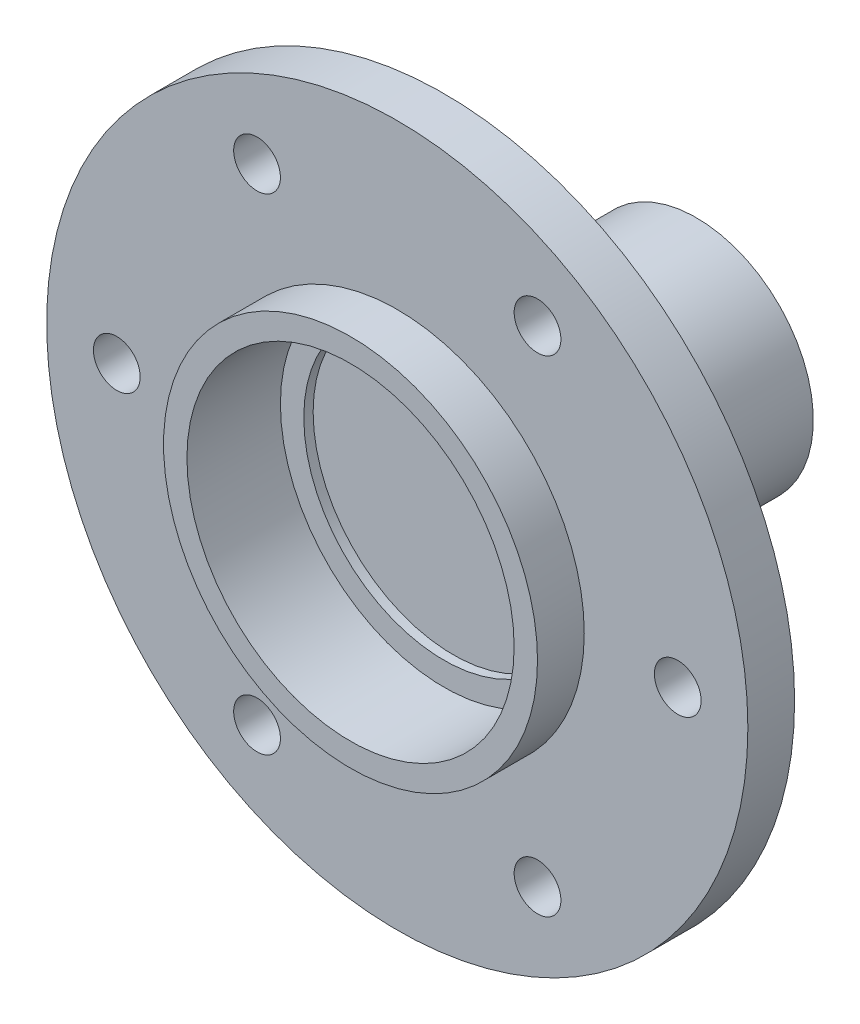
SolidWorks part; units mm, degrees
material "Gray Cast Iron"
ref_plane "Front Plane" through (0, 0, 0) normal (0, 0, 1) x (1, 0, 0)
ref_plane "Top Plane" through (0, 0, 0) normal (0, 1, 0) x (1, 0, 0)
ref_plane "Right Plane" through (0, 0, 0) normal (1, 0, 0) x (0, 0, -1)
sketch "Sketch1" plane through (0, 0, 0) normal (0, 0, 1) x (1, 0, 0)
  circle A0 centre (0, 0) radius 75
  dimension "D1" = 150
extrude "Boss-Extrude1" add sketch "Sketch1" along normal blind 10
sketch "Sketch2" plane through (0, 0, 0) normal (0, 0, -1) x (-1, 0, 0)
  circle A0 centre (0, 0) radius 45
  dimension "D1" = 90
extrude "Boss-Extrude2" add sketch "Sketch2" along normal blind 10
sketch "Sketch3" plane through (0, 0, -10) normal (0, 0, -1) x (-1, 0, 0)
  circle A0 centre (0, 0) radius 25
  dimension "D1" = 50
extrude "Boss-Extrude3" add sketch "Sketch3" along normal blind 44
fillet "Fillet1" radius 20 1 edges at (-25, 0, -10) type face fillet first side face at (-25, 0, -10) second side face at (-25, 0, -54)
sketch "Sketch4" plane through (0, 0, 10) normal (0, 0, 1) x (1, 0, 0)
  circle A0 centre (0, 0) radius 40
  dimension "D1" = 80
extrude "Boss-Extrude4" add sketch "Sketch4" along normal blind 10
sketch "Sketch5" plane through (0, 0, 20) normal (0, 0, 1) x (1, 0, 0)
  circle A0 centre (0, 0) radius 35
  dimension "D1" = 70
extrude "Cut-Extrude1" cut sketch "Sketch5" against normal blind 20
sketch "Sketch6" plane through (0, 0, 0) normal (0, 0, 1) x (1, 0, 0)
  circle A0 centre (0, 0) radius 30
  dimension "D1" = 60
extrude "Cut-Extrude2" cut sketch "Sketch6" against normal blind 2
sketch "Sketch7" plane through (0, 0, 10) normal (0, 0, 1) x (1, 0, 0)
  circle A0 centre (0, 0) radius 60 construction
  circle A1 centre (60, 0) radius 5
  circle A2 centre (30, -51.9615) radius 5
  circle A3 centre (-30, -51.9615) radius 5
  circle A4 centre (-60, 0) radius 5
  circle A5 centre (-30, 51.9615) radius 5
  circle A6 centre (30, 51.9615) radius 5
  point P17 (0, 0)
  dimension "D1" = 120
  dimension "D2" = 10
  dimension "D3" = 6
extrude "Cut-Extrude3" cut sketch "Sketch7" against normal through all
